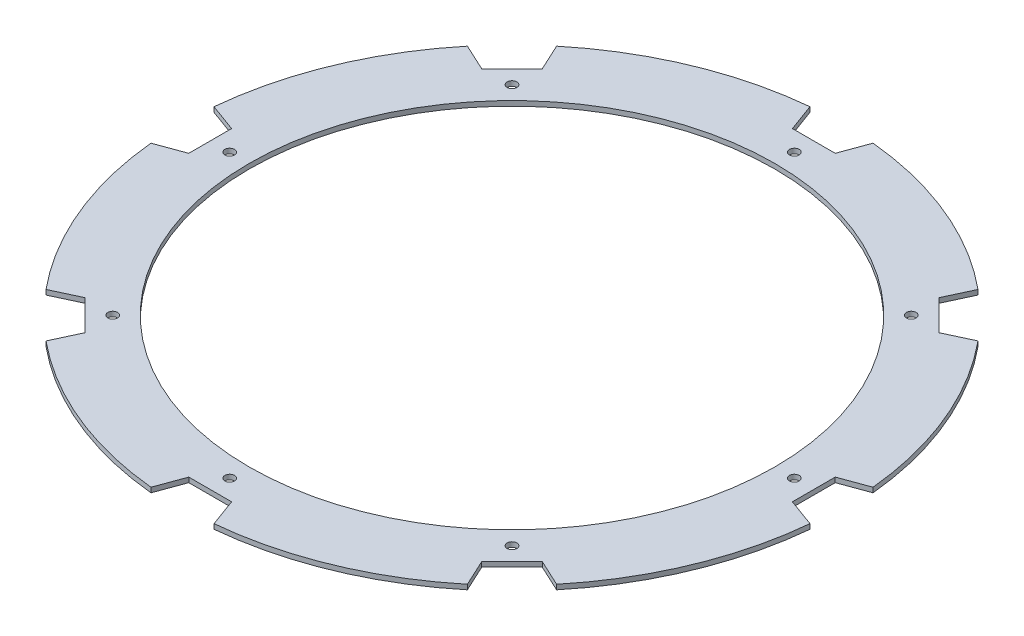
SolidWorks part; units mm, degrees
ref_plane "Front Plane" through (0, 0, 0) normal (0, 0, 1) x (1, 0, 0)
ref_plane "Top Plane" through (0, 0, 0) normal (0, 1, 0) x (1, 0, 0)
ref_plane "Right Plane" through (0, 0, 0) normal (1, 0, 0) x (0, 0, -1)
sketch "Sketch2" plane through (0, 0, 0) normal (0, 1, 0) x (1, 0, 0)
  line L0 (-215.9, 0) -> (-171.45, 0) construction
  line L1 (-171.45, 0) -> (0, 0) construction
  line L2 (0, 0) -> (171.45, 0) construction
  line L3 (171.45, 0) -> (215.9, 0) construction
  line L4 (-214.9183, 20.5652) -> (-196.85, 13.97)
  line L5 (-196.85, 13.97) -> (-196.85, -13.97)
  line L6 (-196.85, -13.97) -> (-214.9175, -20.574)
  circle A0 centre (0, 0) radius 171.45
  circle A1 centre (0, 0) radius 215.9
  circle A2 centre (-184.15, 0) radius 3.175
  point P10 (-196.85, 0)
  point P13 (-196.85, 0)
  point P15 (-171.45, 0)
  dimension "D1" = 342.9
  dimension "D2" = 431.8
  dimension "D7" = 6.35
  dimension "D3" = 27.94
  dimension "D4" = 6.5952
  dimension "D5" = 6.604
  dimension "D6" = 25.4
  dimension "D8" = 12.7
extrude "Boss-Extrude1" add sketch "Sketch2" along normal blind 3.175 contours L6 A1 L4 L5 A2 A0 region at (10.0035, 0, -209.5617)
pattern_circular "CirPattern1" count 8 over 360 about axis through (0, 3.175, 0) along (0, -1, 0) reverse direction yes of face at (-184.15, 3.175, 3.175) of face at (-196.85, 1.5875, 0) of face at (-205.8837, 1.5875, 17.272) of face at (-205.8842, 1.5875, -17.2676)
sketch "Sketch3" plane through (0, 3.175, 0) normal (0, 1, 0) x (1, 0, 0)
  line L0 (-196.85, 13.97) -> (-196.85, -13.97) construction
  line L1 (0, 0) -> (-171.45, 0) construction
  line L2 (-171.45, 0) -> (-196.85, 0) construction
  line L3 (-196.85, 0) -> (-228.5886, 0) construction
  circle A0 centre (0, 0) radius 171.45 construction
  point P0 (-196.85, 0)
  point P1 (0, 0)
  point P4 (-171.45, 0)
